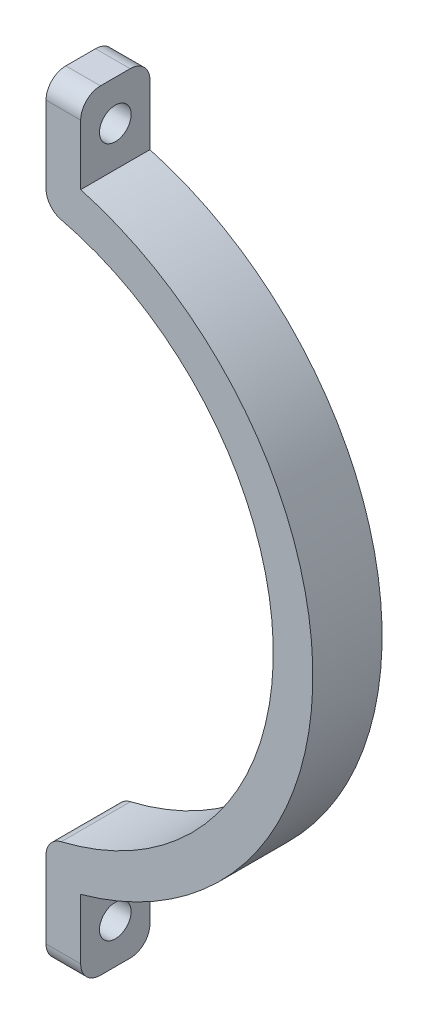
SolidWorks part; units mm, degrees
ref_plane "前视基准面" through (0, 0, 0) normal (0, 0, 1) x (1, 0, 0)
ref_plane "上视基准面" through (0, 0, 0) normal (0, 1, 0) x (1, 0, 0)
ref_plane "右视基准面" through (0, 0, 0) normal (1, 0, 0) x (0, 0, -1)
sketch "草图1" plane through (0, 0, 0) normal (0, 0, 1) x (1, 0, 0)
  line L0 (0, 148.5) -> (0, -94.9538) construction
  line L1 (105, -148.5) -> (-105, -148.5) construction
  line L2 (105, -148.5) -> (105, 148.5) construction
  line L3 (105, 148.5) -> (-105, 148.5) construction
  line L4 (-105, -148.5) -> (-105, 148.5) construction
  line L5 (105, -148.5) -> (-105, 148.5) construction
  line L6 (105, 148.5) -> (-105, -148.5) construction
  line L7 (35.8892, 121.6645) -> (-35.8892, 121.6645)
  line L8 (-35.8892, 121.6645) -> (-66.9017, 102.292)
  line L9 (-75, 40.9339) -> (-75, 31.2613)
  line L10 (-66.9017, 102.292) -> (-66.9017, 52.8701)
  line L11 (75, 40.9339) -> (75, 31.2613)
  line L12 (66.9017, 102.292) -> (66.9017, 52.8701)
  line L13 (35.8892, 121.6645) -> (66.9017, 102.292)
  line L14 (-75, 31.2613) -> (75, 31.2613)
  line L15 (-60, -148.5) -> (-60, -91.8129)
  line L16 (-75, 23.94) -> (75, 23.94)
  line L17 (-75, 23.94) -> (-75, 10.5626)
  line L18 (-38.8455, -105.5906) -> (-66.4608, -113.7617)
  line L19 (-66.4608, -113.7617) -> (-70.1743, -102.7328)
  line L20 (75, 23.94) -> (75, 10.5626)
  line L21 (66.4608, -113.7617) -> (70.1743, -102.7328)
  line L22 (38.8455, -105.5906) -> (66.4608, -113.7617)
  line L23 (-105, 93.0519) -> (105, 93.0519)
  line L24 (-105, 63.0519) -> (105, 63.0519)
  line L25 (-105, -90.0629) -> (-70.5337, -90.0629)
  line L26 (-105, -60.0629) -> (-67.4027, -60.0629)
  line L27 (60, -148.5) -> (60, 148.5)
  line L28 (-60, -58.3129) -> (-45, -58.3129)
  line L29 (-60, -61.8129) -> (-45, -61.8129)
  line L30 (-36, -58.3129) -> (-21, -58.3129)
  line L31 (-36, -61.8129) -> (-21, -61.8129)
  line L32 (-60, -88.3129) -> (-45, -88.3129)
  line L33 (-60, -91.8129) -> (-45, -91.8129)
  line L34 (-36, -88.3129) -> (-21, -88.3129)
  line L35 (-36, -91.8129) -> (-21, -91.8129)
  line L36 (-60, -58.3129) -> (-60, 148.5)
  line L37 (-19.25, -90.0629) -> (105, -90.0629)
  line L38 (-19.25, -60.0629) -> (19.25, -60.0629)
  line L39 (-60, -88.3129) -> (-60, -61.8129)
  line L40 (21, -58.3129) -> (36, -58.3129)
  line L41 (45, -58.3129) -> (60, -58.3129)
  line L42 (60, -61.8129) -> (45, -61.8129)
  line L43 (36, -61.8129) -> (21, -61.8129)
  line L44 (21, -88.3129) -> (36, -88.3129)
  line L45 (21, -91.8129) -> (36, -91.8129)
  line L46 (45, -88.3129) -> (60, -88.3129)
  line L47 (45, -91.8129) -> (60, -91.8129)
  line L48 (37.75, -60.0629) -> (43.25, -60.0629)
  line L49 (58.25, -60.0629) -> (105, -60.0629)
  line L50 (-60, 94.8019) -> (-45, 94.8019)
  line L51 (-36, 94.8019) -> (-21, 94.8019)
  line L52 (-60, 91.3019) -> (-45, 91.3019)
  line L53 (-36, 91.3019) -> (-21, 91.3019)
  line L54 (-60, 64.8019) -> (-45, 64.8019)
  line L55 (-60, 61.3019) -> (-45, 61.3019)
  line L56 (-36, 64.8019) -> (-21, 64.8019)
  line L57 (-36, 61.3019) -> (-21, 61.3019)
  line L58 (21, 94.8019) -> (36, 94.8019)
  line L59 (21, 91.3019) -> (36, 91.3019)
  line L60 (45, 94.8019) -> (60, 94.8019)
  line L61 (45, 91.3019) -> (60, 91.3019)
  line L62 (21, 61.3019) -> (36, 61.3019)
  line L63 (21, 64.8019) -> (36, 64.8019)
  line L64 (45, 61.3019) -> (60, 61.3019)
  line L65 (45, 64.8019) -> (60, 64.8019)
  line L66 (-33.1709, -104.7687) -> (33.1709, -104.7687)
  line L67 (0, -104.7687) -> (0, -148.5) construction
  arc A0 (-75, 40.9339) -> (-66.9017, 52.8701) centre (-79.7474, 52.8701) ccw
  arc A1 (75, 40.9339) -> (66.9017, 52.8701) centre (79.7474, 52.8701) cw
  arc A3 (-60, -88.3129) -> (-60, -91.8129) centre (-60, -90.0629) ccw
  arc A4 (-60, -58.3129) -> (-60, -61.8129) centre (-60, -60.0629) ccw
  circle A5 centre (-60, 63.0519) radius 1.75
  circle A6 centre (-60, 93.0519) radius 1.75
  circle A7 centre (60, 93.0519) radius 1.75
  circle A8 centre (60, 63.0519) radius 1.75
  arc A9 (60, -91.8129) -> (60, -88.3129) centre (60, -90.0629) ccw
  arc A10 (60, -61.8129) -> (60, -58.3129) centre (60, -60.0629) ccw
  arc A11 (-36, -58.3129) -> (-36, -61.8129) centre (-36, -60.0629) ccw
  arc A12 (-36, -88.3129) -> (-36, -91.8129) centre (-36, -90.0629) ccw
  arc A13 (36, -61.8129) -> (36, -58.3129) centre (36, -60.0629) ccw
  arc A14 (36, -91.8129) -> (36, -88.3129) centre (36, -90.0629) ccw
  arc A15 (-45, -61.8129) -> (-45, -58.3129) centre (-45, -60.0629) ccw
  arc A16 (-21, -61.8129) -> (-21, -58.3129) centre (-21, -60.0629) ccw
  arc A17 (-45, -91.8129) -> (-45, -88.3129) centre (-45, -90.0629) ccw
  arc A18 (-21, -91.8129) -> (-21, -88.3129) centre (-21, -90.0629) ccw
  arc A19 (45, -58.3129) -> (45, -61.8129) centre (45, -60.0629) ccw
  arc A20 (21, -58.3129) -> (21, -61.8129) centre (21, -60.0629) ccw
  arc A21 (21, -88.3129) -> (21, -91.8129) centre (21, -90.0629) ccw
  arc A22 (45, -88.3129) -> (45, -91.8129) centre (45, -90.0629) ccw
  circle A23 centre (-36, 93.0519) radius 1.75
  circle A24 centre (-36, 63.0519) radius 1.75
  circle A25 centre (36, 93.0519) radius 1.75
  circle A26 centre (36, 63.0519) radius 1.75
  circle A27 centre (-45, 93.0519) radius 1.75
  circle A28 centre (-21, 93.0519) radius 1.75
  circle A29 centre (-45, 63.0519) radius 1.75
  circle A30 centre (-21, 63.0519) radius 1.75
  circle A31 centre (21, 93.0519) radius 1.75
  circle A32 centre (21, 63.0519) radius 1.75
  circle A33 centre (45, 93.0519) radius 1.75
  circle A34 centre (45, 63.0519) radius 1.75
  arc A35 (33.1709, -104.7687) -> (38.8455, -105.5906) centre (33.1709, -124.7687) cw
  arc A36 (-33.1709, -104.7687) -> (-38.8455, -105.5906) centre (-33.1709, -124.7687) ccw
  spline S0 degree 3 poles (-75, 10.5626) (-72.6959, 1.9073) (-70.3396, -13.3728) (-67.1028, -43.6255) (-66.7657, -72.9327) (-71.8903, -95.1489) (-70.1743, -102.7328) knots 0 0 0 0 0.235247 0.406294 0.801186 1 1 1 1
  spline S1 degree 3 poles (75, 10.5626) (72.6959, 1.9073) (70.3396, -13.3728) (67.1028, -43.6255) (66.7657, -72.9327) (71.8903, -95.1489) (70.1743, -102.7328) knots 0 0 0 0 0.235247 0.406294 0.801186 1 1 1 1
  point P0 (0, 0)
  point P27 (0, 121.6645)
  point P42 (0, -94.0966)
  dimension "D1" = 60
  dimension "D4" = 20
  dimension "D5" = 24
  dimension "D7" = 24
  dimension "D9" = 15
  dimension "D10" = 15
  dimension "D13" = 24
  dimension "D17" = 15
  dimension "D2" = 30
  dimension "D3" = 30
  dimension "D6" = 24
  dimension "D8" = 24
  dimension "D11" = 15
  dimension "D12" = 15
  dimension "D14" = 24
  dimension "D15" = 24
  dimension "D16" = 24
  dimension "D18" = 15
  dimension "D19" = 15
  dimension "D20" = 15
  dimension "D21" = 15
  dimension "D22" = 15
  dimension "D23" = 15
  dimension "D24" = 15
  dimension "D25" = 15
  dimension "D26" = 15
  dimension "D27" = 15
  dimension "D28" = 15
  dimension "D29" = 3.5
  dimension "D30" = 3.5
  dimension "D31" = 3.5
extrude "凸台-拉伸1" add sketch "草图1" along normal blind 3 contours A34 L24 A26 L62 A32 A30 L57 A24 A29 L55 L36 L14 L27 L64 | A5 L24 L10 A0 L9 L14 L36 | A6 L23 L10 L24 A5 L36 | A6 L36 L8 L10 L23 | A33 L60 L27 L13 L7 L8 L36 L50 A27 L23 A23 L51 A28 A31 L58 A25 | A34 L65 L27 L61 A33 L23 A25 L59 A31 A28 L53 A23 A27 L52 L36 L54 A29 L24 A24 L56 A30 A32 L63 A26 | A7 L23 L12 L13 L27 | A8 L24 L12 L23 A7 L27 | A8 L27 L14 L11 A1 L12 L24 | A22 L46 L27 L42 A19 A13 L43 A20 A16 L31 A11 L30 L40 L41 L16 L36 L28 A15 L29 L39 L32 A17 L33 L15 L18 L22 L47 A14 L45 A21 A18 L35 A12 L34 | L17 S0 L19 L18 L15 A3 L39 A4 L36 L16 | S1 L20 L16 L27 A10 L49 | S1 L49 A10 L27 A9 L37 | S1 L37 A9 L27 L22 L21 region at (0, 106.7597, 0) region at (63.3118, 98.9762, 0) region at (-63.3118, 98.9762, 0) region at (63.5153, 78.0519, 0) region at (-63.5153, 78.0519, 0) region at (65.7633, 44.067, 0) region at (0, 78.0519, 0) region at (-65.7633, 44.067, 0) region at (0, 46.6707, 0) region at (0, -40.0712, 0) region at (65.6849, -11.6712, 0) region at (-65.3451, -38.0027, 0) region at (64.4303, -76.0355, 0) region at (65.0264, -100.7629, 0)
sketch "草图7" plane through (0, 0, 0) normal (0, 0, -1) x (-1, 0, 0)
  line L0 (0, 121.6645) -> (0, -104.7687) construction
  line L1 (-35.8892, 121.6645) -> (35.8892, 121.6645) construction
  line L2 (33.1709, -104.7687) -> (-33.1709, -104.7687) construction
  line L3 (0, 41.2613) -> (-21, 41.2613) construction
  line L4 (0, 41.2613) -> (21, 41.2613) construction
  line L5 (0, 13.94) -> (-21, 13.94) construction
  line L6 (0, 13.94) -> (21, 13.94) construction
  line L7 (75, 23.94) -> (-75, 23.94) construction
  line L8 (75, 31.2613) -> (-75, 31.2613) construction
  circle A0 centre (-21, 41.2613) radius 2.25
  circle A1 centre (21, 41.2613) radius 2.25
  circle A2 centre (-21, 13.94) radius 2.25
  circle A3 centre (21, 13.94) radius 2.25
  dimension "D1" = 10
  dimension "D2" = 10
extrude "切除-拉伸2" cut sketch "草图7" against normal through all
sketch "草图8" plane through (0, 0, 3) normal (0, 0, 1) x (1, 0, 0)
  line L0 (0, 121.6645) -> (0, -1.9696) construction
  line L1 (35.8892, 121.6645) -> (-35.8892, 121.6645) construction
  line L2 (-33.1709, -104.7687) -> (33.1709, -104.7687) construction
  line L3 (-33.409, 20.409) -> (-12.6214, -0.3786)
  line L4 (31.818, -51.182) -> (-31.818, -51.182)
  line L5 (35, -48) -> (35, 15.6418)
  line L8 (-35, 18.818) -> (-12.6214, -3.5605) construction
  line L9 (-33.409, -52.773) -> (-12.5737, -31.9377)
  line L10 (-36.591, 17.227) -> (-15.8034, -3.5605)
  line L11 (33.4105, 20.4105) -> (12.573, -0.427)
  line L12 (15.803, -3.5609) -> (36.5881, 17.2241)
  line L13 (31.8195, 18.8195) -> (-31.818, 18.818)
  line L14 (-15.8038, -28.8038) -> (-36.591, -49.591)
  line L15 (12.5534, -31.9174) -> (33.409, -52.773)
  line L16 (34.9993, 18.8173) -> (12.6207, -3.5613) construction
  line L17 (0, -30.3951) -> (0, -104.7687) construction
  line L18 (-35, -48) -> (-35, 15.636)
  line L19 (-11.9624, -1.9696) -> (-14.2124, -1.9696) construction
  line L20 (15.8034, -28.8034) -> (36.591, -49.591)
  line L21 (14.2117, -30.3951) -> (11.9607, -30.3951) construction
  line L22 (14.2117, -30.3951) -> (14.2117, -28.1441) construction
  line L23 (14.2117, -1.9696) -> (11.9612, -1.9696) construction
  line L24 (-14.2124, -30.3951) -> (-14.2124, -28.1446) construction
  line L25 (14.2117, -30.3951) -> (12.62, -28.8034) construction
  line L26 (14.2117, -1.9696) -> (12.6204, -3.5609) construction
  line L27 (12.6207, -28.8027) -> (35, -51.182) construction
  line L28 (-12.6215, -3.5606) -> (-14.2124, -1.9696) construction
  line L29 (-14.2124, -4.2196) -> (-14.2124, -1.9696) construction
  line L30 (-12.6214, -28.8034) -> (-35, -51.182) construction
  line L31 (-12.6211, -28.8037) -> (-14.2124, -30.3951) construction
  line L32 (-11.9619, -30.3951) -> (-14.2124, -30.3951) construction
  line L33 (14.2117, -4.2201) -> (14.2117, -1.9696) construction
  line L34 (11.0312, -30.3951) -> (0, -30.3951) construction
  arc A0 (-33.409, 20.409) -> (-36.591, 17.227) centre (-35, 18.818) ccw
  arc A1 (36.5881, 17.2241) -> (33.4105, 20.4105) centre (34.9993, 18.8173) ccw
  arc A2 (-36.591, -49.591) -> (-33.409, -52.773) centre (-35, -51.182) ccw
  arc A3 (33.409, -52.773) -> (36.591, -49.591) centre (35, -51.182) ccw
  arc A4 (-15.8034, -3.5605) -> (-12.6214, -0.3786) centre (-14.2124, -1.9696) ccw
  arc A5 (12.6692, -0.3308) -> (15.803, -3.5609) centre (14.2117, -1.9696) ccw
  arc A6 (-12.6699, -32.0338) -> (-15.8038, -28.8038) centre (-14.2124, -30.3951) ccw
  arc A7 (15.8034, -28.8034) -> (12.6894, -32.0534) centre (14.2117, -30.3951) ccw
  circle A8 centre (-0.0004, -16.1823) radius 8
  point P6 (0, -16.182)
  point P13 (-0.0004, -16.1823)
extrude "切除-拉伸3" cut sketch "草图8" against normal through all contours L10 A4 L3 A0 | L11 A5 L12 A1 | L20 A7 L15 A3 | L9 A6 L14 A2 | A8 region at (-24.6062, 8.4242, 3) region at (24.6054, 8.4234, 3) region at (-24.6061, -40.7881, 3) region at (24.6056, -40.7877, 3) region at (-0.0004, -16.1823, 3)
sketch "草图9" plane through (0, 0, 3) normal (0, 0, 1) x (1, 0, 0)
  line L0 (-70.7828, -98.747) -> (70.7828, -98.747) construction
  line L1 (0, -98.747) -> (0, -104.7687) construction
  line L2 (55, -100.497) -> (20, -100.497)
  line L3 (-55, -96.997) -> (-20, -96.997)
  line L4 (-55, -100.497) -> (-20, -100.497)
  line L5 (-33.1709, -104.7687) -> (33.1709, -104.7687) construction
  line L6 (55, -96.997) -> (20, -96.997)
  arc A0 (-55, -96.997) -> (-55, -100.497) centre (-55, -98.747) ccw
  arc A1 (-20, -100.497) -> (-20, -96.997) centre (-20, -98.747) ccw
  arc A2 (20, -100.497) -> (20, -96.997) centre (20, -98.747) cw
  arc A3 (55, -96.997) -> (55, -100.497) centre (55, -98.747) cw
  spline S0 degree 3 poles (-75, 10.5626) (-72.6959, 1.9073) (-70.3396, -13.3728) (-67.1028, -43.6255) (-66.7657, -72.9327) (-71.8903, -95.1489) (-70.1743, -102.7328) knots 0 0 0 0 0.235247 0.406294 0.801186 1 1 1 1 construction
  spline S1 degree 3 poles (75, 10.5626) (72.6959, 1.9073) (70.3396, -13.3728) (67.1028, -43.6255) (66.7657, -72.9327) (71.8903, -95.1489) (70.1743, -102.7328) knots 0 0 0 0 0.235247 0.406294 0.801186 1 1 1 1 construction
  dimension "D1" = 35
  dimension "D2" = 20
extrude "切除-拉伸4" cut sketch "草图9" against normal blind 3
sketch "草图10" plane through (0, 0, 3) normal (0, 0, 1) x (1, 0, 0)
  line L0 (-21, -60.0629) -> (-21, -90.0629) construction
  line L1 (21, -60.0629) -> (21, -90.0629) construction
  line L2 (-21, -75.0629) -> (-17.5, -75.0629) construction
  line L4 (12.5, -80.0629) -> (-12.5, -80.0629)
  line L6 (12.5, -70.0629) -> (-12.5, -70.0629)
  line L11 (17.5, -75.0629) -> (21, -75.0629) construction
  arc A0 (-12.5, -70.0629) -> (-12.5, -80.0629) centre (-12.5, -75.0629) ccw
  arc A1 (12.5, -80.0629) -> (12.5, -70.0629) centre (12.5, -75.0629) ccw
  point P11 (0, -75.0629)
extrude "切除-拉伸5" cut sketch "草图10" against normal blind 3
sketch "草图11" plane through (0, 0, 3) normal (0, 0, 1) x (1, 0, 0)
  line L0 (-21, 93.0519) -> (-21, 63.0519) construction
  line L1 (21, 93.0519) -> (21, 63.0519) construction
  line L2 (-21, 78.0519) -> (-20, 78.0519) construction
  line L4 (15, 73.0519) -> (-15, 73.0519)
  line L6 (15, 83.0519) -> (-15, 83.0519)
  line L10 (20, 78.0519) -> (21, 78.0519) construction
  arc A0 (-15, 83.0519) -> (-15, 73.0519) centre (-15, 78.0519) ccw
  arc A1 (15, 73.0519) -> (15, 83.0519) centre (15, 78.0519) ccw
  point P10 (0, 78.0519)
  dimension "D1" = 30
extrude "切除-拉伸8" cut sketch "草图11" against normal blind 3
sketch "草图12" plane through (0, 0, 3) normal (0, 0, 1) x (1, 0, 0)
  line L0 (0, 121.6645) -> (0, 83.0519) construction
  line L1 (35.8892, 121.6645) -> (-35.8892, 121.6645) construction
  line L2 (15, 83.0519) -> (-15, 83.0519) construction
  circle A0 centre (0, 106.3718) radius 11 construction
  circle A1 centre (0, 106.3718) radius 8 construction
  circle A2 centre (0, 114.3718) radius 1.7
  circle A3 centre (0, 98.3718) radius 1.7
  circle A4 centre (8, 106.3718) radius 1.7
  circle A5 centre (-8, 106.3718) radius 1.7
extrude "切除-拉伸9" cut sketch "草图12" against normal blind 3
sketch "草图13" plane through (0, 0, 3) normal (0, 0, 1) x (1, 0, 0)
  line L0 (0, -104.7687) -> (0, -80.0629) construction
  line L1 (-33.1709, -104.7687) -> (33.1709, -104.7687) construction
  line L2 (-12.5, -80.0629) -> (12.5, -80.0629) construction
  circle A0 centre (0, -92.4158) radius 8 construction
  circle A1 centre (0, -84.4158) radius 1.7
  circle A2 centre (8, -92.4158) radius 1.7
  circle A3 centre (0, -100.4158) radius 1.7
  circle A4 centre (-8, -92.4158) radius 1.7
extrude "切除-拉伸11" cut sketch "草图13" against normal blind 3
sketch "草图14" plane through (0, 0, 3) normal (0, 0, 1) x (1, 0, 0)
  line L0 (0, 23.94) -> (0, -104.7687) construction
  line L1 (-55.4755, 8.9197) -> (-55.4755, -46.0803)
  line L2 (-58.9755, 8.9197) -> (-58.9755, -46.0803)
  line L3 (-75, 23.94) -> (75, 23.94) construction
  line L4 (-33.1709, -104.7687) -> (33.1709, -104.7687) construction
  line L5 (58.9755, 8.9197) -> (58.9755, -46.0803)
  line L6 (55.4755, 8.9197) -> (55.4755, -46.0803)
  arc A0 (-55.4755, 8.9197) -> (-58.9755, 8.9197) centre (-57.2255, 8.9197) ccw
  arc A1 (-58.9755, -46.0803) -> (-55.4755, -46.0803) centre (-57.2255, -46.0803) ccw
  arc A2 (58.9755, -46.0803) -> (55.4755, -46.0803) centre (57.2255, -46.0803) cw
  arc A3 (55.4755, 8.9197) -> (58.9755, 8.9197) centre (57.2255, 8.9197) cw
extrude "切除-拉伸12" cut sketch "草图14" against normal through all
fillet "圆角1" radius 2 2 edges at (75, 31.2613, 1.5) (-75, 31.2613, 1.5)
fillet "圆角2" radius 2 2 edges at (-75, 23.94, 1.5) (75, 23.94, 1.5)
sketch "草图15" plane through (0, 0, 0) normal (0, 0, -1) x (-1, 0, 0)
  line L0 (0, 121.6645) -> (0, 31.2613) construction
  line L1 (-35.8892, 121.6645) -> (35.8892, 121.6645) construction
  line L2 (73, 31.2613) -> (-73, 31.2613) construction
  line L3 (-27.5188, 121.6645) -> (-63.6963, 99.0657) construction
  line L4 (-35.8892, 121.6645) -> (-66.9017, 102.292) construction
  line L5 (-61.1842, 102.4035) -> (-34.7748, 118.9006)
  line L6 (-59.5948, 99.8591) -> (-33.1854, 116.3562)
  line L7 (27.5188, 121.6645) -> (63.6963, 99.0657) construction
  line L8 (59.5948, 99.8591) -> (33.1854, 116.3562)
  line L9 (61.1842, 102.4035) -> (34.7748, 118.9006)
  arc A0 (-61.1842, 102.4035) -> (-59.5948, 99.8591) centre (-60.3895, 101.1313) ccw
  arc A1 (-33.1854, 116.3562) -> (-34.7748, 118.9006) centre (-33.9801, 117.6284) ccw
  arc A2 (33.1854, 116.3562) -> (34.7748, 118.9006) centre (33.9801, 117.6284) cw
  arc A3 (61.1842, 102.4035) -> (59.5948, 99.8591) centre (60.3895, 101.1313) cw
extrude "切除-拉伸13" cut sketch "草图15" against normal through all
sketch "草图16" plane through (0, 0, 0) normal (0, 0, -1) x (-1, 0, 0)
  line L0 (0, 121.6645) -> (0, 31.2613) construction
  line L1 (-35.8892, 121.6645) -> (35.8892, 121.6645) construction
  line L2 (73, 31.2613) -> (-73, 31.2613) construction
  line L3 (-21, 41.2613) -> (-66.71, 41.2613) construction
  line L4 (-61.517, 42.7613) -> (-32.0563, 42.7613)
  line L5 (-61.517, 39.7613) -> (-32.0563, 39.7613)
  line L6 (21, 41.2613) -> (66.71, 41.2613) construction
  line L7 (61.517, 39.7613) -> (32.0563, 39.7613)
  line L8 (61.517, 42.7613) -> (32.0563, 42.7613)
  arc A0 (-61.517, 42.7613) -> (-61.517, 39.7613) centre (-61.517, 41.2613) ccw
  arc A1 (-32.0563, 39.7613) -> (-32.0563, 42.7613) centre (-32.0563, 41.2613) ccw
  arc A2 (32.0563, 39.7613) -> (32.0563, 42.7613) centre (32.0563, 41.2613) cw
  arc A3 (61.517, 42.7613) -> (61.517, 39.7613) centre (61.517, 41.2613) cw
extrude "切除-拉伸14" cut sketch "草图16" against normal through all
sketch "草图17" plane through (0, 0, 0) normal (0, 0, -1) x (-1, 0, 0)
  text T0 "Y" font "黑体" height in points 72
extrude "切除-拉伸15" cut sketch "草图17" against normal through all
sketch "草图18" plane through (0, 0, 0) normal (0, 0, -1) x (-1, 0, 0)
  text T0 "H" font "黑体" height in points 72
extrude "切除-拉伸16" cut sketch "草图18" against normal through all
ref_plane "基准面1" through (0, 0, -10) normal (0, 0, -1) x (-1, 0, 0)
sketch "草图19" plane through (0, 0, -10) normal (0, 0, -1) x (-1, 0, 0)
  line L0 (-58.9755, -46.0803) -> (-58.9755, 8.9197) construction
  line L1 (-55.4755, 8.9197) -> (-55.4755, -46.0803) construction
  line L2 (-58.9755, -30.086) -> (-58.9755, -15.086)
  line L3 (-55.4755, -15.086) -> (-55.4755, -30.086)
  line L4 (-57.2255, -15.086) -> (-57.2255, -30.086) construction
  line L5 (-55.4755, -15.086) -> (-55.4755, -30.086)
  line L6 (-58.9755, -15.086) -> (-58.9755, -30.086)
  line L7 (-61.7255, -34.086) -> (-89.4178, -34.086) construction
  line L8 (-61.7255, -34.086) -> (-52.7255, -34.086)
  line L10 (-61.7255, -11.086) -> (-52.7255, -11.086)
  line L11 (-52.7255, -34.086) -> (-52.7255, -11.086)
  line L12 (-61.7255, -34.086) -> (-52.7255, -11.086) construction
  line L13 (-58.9755, -18.1137) -> (-52.7255, -34.086) construction
  line L14 (-75, 21.94) -> (-75, 10.5626) construction
  line L15 (-61.7255, -11.086) -> (-75, -11.086)
  line L17 (-61.7255, -34.086) -> (-75, -34.086)
  line L18 (-75, -11.086) -> (-75, -34.086)
  arc A0 (-58.9755, -46.0803) -> (-55.4755, -46.0803) centre (-57.2255, -46.0803) ccw construction
  arc A1 (-55.4755, 8.9197) -> (-58.9755, 8.9197) centre (-57.2255, 8.9197) ccw construction
  arc A2 (-58.9755, -46.0803) -> (-55.4755, -46.0803) centre (-57.2255, -46.0803) ccw
  arc A3 (-55.4755, 8.9197) -> (-58.9755, 8.9197) centre (-57.2255, 8.9197) ccw
  arc A4 (-55.4755, -15.086) -> (-58.9755, -15.086) centre (-57.2255, -15.086) ccw
  arc A5 (-58.9755, -30.086) -> (-55.4755, -30.086) centre (-57.2255, -30.086) ccw
  point P7 (-57.2255, -22.586)
  dimension "D1" = 15
  dimension "D2" = 0
extrude "凸台-拉伸2" add sketch "草图19" along normal blind 4 separate body contours L15 L18 L17 L8 L11 L10 A5 L2 A4 L3 region at (64.7786, -22.586, -10)
sketch "草图20" plane through (0, 0, -14) normal (0, 0, -1) x (-1, 0, 0)
  line L0 (-52.7255, -34.086) -> (-75, -34.086) construction
  line L1 (-75, -11.086) -> (-71, -11.086)
  line L2 (-75, -11.086) -> (-75, -34.086)
  line L3 (-75, -34.086) -> (-71, -34.086)
  line L4 (-71, -11.086) -> (-71, -34.086)
extrude "凸台-拉伸3" add sketch "草图20" along normal blind 5
sketch "草图21" plane through (0, 0, -19) normal (0, 0, -1) x (-1, 0, 0)
  line L0 (-71, -22.586) -> (-170.2086, -22.586) construction
  line L1 (-71, -34.086) -> (-71, -11.086) construction
  line L2 (-75, -11.086) -> (-75, -34.086) construction
  line L3 (-102.0333, -61.5135) -> (-98.5333, -61.5135)
  line L4 (-108.0333, 16.3416) -> (-108.0333, 4.9579)
  line L5 (-102.0333, 16.3416) -> (-102.0333, 5.3974)
  line L6 (-111.5333, 16.3416) -> (-111.5333, 8.2553)
  line L7 (-98.5333, 16.3416) -> (-98.5333, 9.1008)
  line L8 (-111.5333, 16.3416) -> (-108.0333, 16.3416)
  line L9 (-102.0333, 16.3416) -> (-98.5333, 16.3416)
  line L11 (-111.5333, -61.5135) -> (-108.0333, -61.5135)
  line L12 (-111.5333, -53.4272) -> (-111.5333, -61.5135)
  line L13 (-108.0333, -50.1298) -> (-108.0333, -61.5135)
  line L14 (-102.0333, -50.5693) -> (-102.0333, -61.5135)
  line L15 (-98.5333, -54.2727) -> (-98.5333, -61.5135)
  arc A0 (-108.0333, 4.9579) -> (-108.0333, -50.1298) centre (-103, -22.586) ccw
  arc A1 (-111.5333, 8.2553) -> (-111.5333, -53.4272) centre (-103, -22.586) ccw
  arc A2 (-102.0333, -50.5693) -> (-102.0333, 5.3974) centre (-103, -22.586) ccw
  arc A3 (-98.5333, -54.2727) -> (-98.5333, 9.1008) centre (-103, -22.586) ccw
  dimension "D1" = 3.5
  dimension "D2" = 3.5
  dimension "D3" = 6
extrude "凸台-拉伸4" add sketch "草图21" along normal blind 7
sketch "草图22" plane through (0, 0, -19) normal (0, 0, 1) x (1, 0, 0)
  line L0 (75, -22.586) -> (75, -34.086) construction
  line L1 (75, -34.086) -> (73.1378, -34.086) construction
  line L2 (98.5333, -54.2727) -> (98.5333, -61.5135) construction
  line L3 (98.5333, -61.5135) -> (102.0333, -61.5135) construction
  line L4 (102.0333, -61.5135) -> (102.0333, -50.5693) construction
  line L5 (73.1378, -11.086) -> (75, -11.086) construction
  line L6 (75, -11.086) -> (75, -22.586) construction
  line L7 (102.0333, 5.3974) -> (102.0333, 16.3416) construction
  line L8 (102.0333, 16.3416) -> (98.5333, 16.3416) construction
  line L9 (98.5333, 16.3416) -> (98.5333, 9.1008) construction
  line L10 (75, -22.586) -> (75, -34.086)
  line L11 (75, -34.086) -> (73.1378, -34.086)
  line L12 (98.5333, -54.2727) -> (98.5333, -61.5135)
  line L13 (98.5333, -61.5135) -> (102.0333, -61.5135)
  line L14 (102.0333, -61.5135) -> (102.0333, -50.5693)
  line L15 (73.1378, -11.086) -> (75, -11.086)
  line L16 (75, -11.086) -> (75, -22.586)
  line L17 (102.0333, 5.3974) -> (102.0333, 16.3416)
  line L18 (102.0333, 16.3416) -> (98.5333, 16.3416)
  line L19 (98.5333, 16.3416) -> (98.5333, 9.1008)
  line L20 (75, -11.086) -> (77.4706, -11.086)
  line L21 (75, -34.086) -> (77.4706, -34.086)
  arc A1 (75, -22.586) -> (102.0333, -50.5693) centre (103, -22.586) ccw construction
  arc A2 (102.0333, 5.3974) -> (75, -22.586) centre (103, -22.586) ccw construction
  arc A5 (75, -22.586) -> (77.4706, -34.086) centre (103, -22.586) ccw
  arc A6 (77.4706, -11.086) -> (75, -22.586) centre (103, -22.586) ccw
  line M9 (75, -11.086) -> (75, -22.586)
  arc M10 (75, -22.586) -> (102.0333, 5.3974) centre (103, -22.586) cw
extrude "凸台-拉伸5" add sketch "草图22" along normal up to surface (9 mm away) contours L20 M9 M10 | A5 L10 L21 region at (75.7352, -31.2369, -19) region at (75.7352, -13.935, -19) up to face at (57.2255, -22.586, -10)
sketch "草图23" plane through (0, 0, -19) normal (0, 0, -1) x (-1, 0, 0)
  line L0 (-71, -22.586) -> (-71, -11.086) construction
  line L1 (-71, -11.086) -> (-73.1378, -11.086) construction
  line L2 (-73.1378, -34.086) -> (-71, -34.086) construction
  line L3 (-71, -34.086) -> (-71, -22.586) construction
  line L4 (-71, -22.586) -> (-71, -11.086)
  line L5 (-71, -11.086) -> (-73.1378, -11.086)
  line L6 (-73.1378, -34.086) -> (-71, -34.086)
  line L7 (-71, -34.086) -> (-71, -22.586)
  arc A0 (-71, -22.586) -> (-73.1378, -11.086) centre (-103, -22.586) ccw construction
  arc A1 (-73.1378, -34.086) -> (-71, -22.586) centre (-103, -22.586) ccw construction
  arc A2 (-71, -22.586) -> (-73.1378, -11.086) centre (-103, -22.586) ccw
  arc A3 (-73.1378, -34.086) -> (-71, -22.586) centre (-103, -22.586) ccw
  arc M1 (-71, -22.586) -> (-73.1378, -34.086) centre (-103, -22.586) cw
  line M2 (-73.1378, -34.086) -> (-71, -34.086)
  line M3 (-71, -34.086) -> (-71, -22.586)
extrude "切除-拉伸17" cut sketch "草图23" against normal up to surface (5 mm away) contours A2 L4 L5 | M3 M1 M2 region at (71.6375, -13.9414, -19) region at (71.6375, -31.2305, -19) up to face at (61.8628, -22.586, -14)
sketch "草图24" plane through (0, 0, -26) normal (0, 0, -1) x (-1, 0, 0)
  line L0 (-73.1378, -11.086) -> (-77.4706, -11.086)
  line L1 (-73.1378, -34.086) -> (-77.4706, -34.086)
  line L6 (-102.0333, -50.5693) -> (-102.0333, -61.5135)
  line L7 (-102.0333, -61.5135) -> (-98.5333, -61.5135)
  line L8 (-98.5333, -61.5135) -> (-98.5333, -54.2727)
  line L9 (-98.5333, 9.1008) -> (-98.5333, 16.3416)
  line L10 (-98.5333, 16.3416) -> (-102.0333, 16.3416)
  line L11 (-102.0333, 16.3416) -> (-102.0333, 5.3974)
  line L12 (-102.0333, -50.5693) -> (-102.0333, -61.5135)
  line L13 (-102.0333, -61.5135) -> (-98.5333, -61.5135)
  line L14 (-98.5333, -61.5135) -> (-98.5333, -54.2727)
  line L15 (-98.5333, 9.1008) -> (-98.5333, 16.3416)
  line L16 (-98.5333, 16.3416) -> (-102.0333, 16.3416)
  line L17 (-102.0333, 16.3416) -> (-102.0333, 5.3974)
  arc A2 (-102.0333, -50.5693) -> (-102.0333, 5.3974) centre (-103, -22.586) ccw
  arc A3 (-98.5333, -54.2727) -> (-98.5333, 9.1008) centre (-103, -22.586) ccw
  arc A4 (-77.4706, -34.086) -> (-77.4706, -11.086) centre (-103, -22.586) ccw
  arc A5 (-73.1378, -34.086) -> (-73.1378, -11.086) centre (-103, -22.586) ccw
  arc M9 (-102.0333, 5.3974) -> (-102.0333, -50.5693) centre (-103, -22.586) cw
  arc M13 (-98.5333, -54.2727) -> (-98.5333, 9.1008) centre (-103, -22.586) ccw
  dimension "D1" = 0
extrude "凸台-拉伸6" add sketch "草图24" along normal blind 5 contours L1 L0 M13 M9 region at (73.7718, -22.586, -26)
sketch "草图25" plane through (0, 0, -31) normal (0, 0, -1) x (-1, 0, 0)
  line L0 (-111.5333, -53.4272) -> (-111.5333, -61.5135) construction
  line L1 (-111.5333, -61.5135) -> (-108.0333, -61.5135) construction
  line L2 (-108.0333, -61.5135) -> (-108.0333, -50.1298) construction
  line L3 (-108.0333, 4.9579) -> (-108.0333, 16.3416) construction
  line L4 (-108.0333, 16.3416) -> (-111.5333, 16.3416) construction
  line L5 (-111.5333, 16.3416) -> (-111.5333, 8.2553) construction
  line L6 (-73.1378, -34.086) -> (-77.4706, -34.086) construction
  line L7 (-102.0333, -50.5693) -> (-102.0333, -61.5135) construction
  line L8 (-102.0333, -61.5135) -> (-98.5333, -61.5135) construction
  line L9 (-98.5333, -61.5135) -> (-98.5333, -54.2727) construction
  line L10 (-77.4706, -34.086) -> (-73.1378, -34.086) construction
  line L11 (-73.1378, -11.086) -> (-77.4706, -11.086) construction
  line L12 (-77.4706, -11.086) -> (-73.1378, -11.086) construction
  line L13 (-98.5333, 9.1008) -> (-98.5333, 16.3416) construction
  line L14 (-98.5333, 16.3416) -> (-102.0333, 16.3416) construction
  line L15 (-102.0333, 16.3416) -> (-102.0333, 5.3974) construction
  line L16 (-111.5333, -53.4272) -> (-111.5333, -61.5135)
  line L17 (-111.5333, -61.5135) -> (-108.0333, -61.5135)
  line L18 (-108.0333, -61.5135) -> (-108.0333, -50.1298)
  line L19 (-108.0333, 4.9579) -> (-108.0333, 16.3416)
  line L20 (-108.0333, 16.3416) -> (-111.5333, 16.3416)
  line L21 (-111.5333, 16.3416) -> (-111.5333, 8.2553)
  line L22 (-73.1378, -34.086) -> (-77.4706, -34.086)
  line L23 (-102.0333, -50.5693) -> (-102.0333, -61.5135)
  line L24 (-102.0333, -61.5135) -> (-98.5333, -61.5135)
  line L25 (-98.5333, -61.5135) -> (-98.5333, -54.2727)
  line L26 (-77.4706, -34.086) -> (-73.1378, -34.086)
  line L27 (-73.1378, -11.086) -> (-77.4706, -11.086)
  line L28 (-77.4706, -11.086) -> (-73.1378, -11.086)
  line L29 (-98.5333, 9.1008) -> (-98.5333, 16.3416)
  line L30 (-98.5333, 16.3416) -> (-102.0333, 16.3416)
  line L31 (-102.0333, 16.3416) -> (-102.0333, 5.3974)
  arc A0 (-111.5333, 8.2553) -> (-111.5333, -53.4272) centre (-103, -22.586) ccw construction
  arc A1 (-108.0333, 4.9579) -> (-108.0333, -50.1298) centre (-103, -22.586) ccw construction
  arc A2 (-98.5333, -54.2727) -> (-73.1378, -34.086) centre (-103, -22.586) ccw construction
  arc A3 (-102.0333, -50.5693) -> (-77.4706, -34.086) centre (-103, -22.586) ccw construction
  arc A4 (-73.1378, -34.086) -> (-73.1378, -11.086) centre (-103, -22.586) ccw construction
  arc A5 (-77.4706, -34.086) -> (-77.4706, -11.086) centre (-103, -22.586) ccw construction
  arc A6 (-73.1378, -11.086) -> (-98.5333, 9.1008) centre (-103, -22.586) ccw construction
  arc A7 (-77.4706, -11.086) -> (-102.0333, 5.3974) centre (-103, -22.586) ccw construction
  arc A8 (-111.5333, 8.2553) -> (-111.5333, -53.4272) centre (-103, -22.586) ccw
  arc A9 (-108.0333, 4.9579) -> (-108.0333, -50.1298) centre (-103, -22.586) ccw
  arc A10 (-98.5333, -54.2727) -> (-73.1378, -34.086) centre (-103, -22.586) ccw
  arc A11 (-102.0333, -50.5693) -> (-77.4706, -34.086) centre (-103, -22.586) ccw
  arc A12 (-73.1378, -34.086) -> (-73.1378, -11.086) centre (-103, -22.586) ccw
  arc A13 (-77.4706, -34.086) -> (-77.4706, -11.086) centre (-103, -22.586) ccw
  arc A14 (-73.1378, -11.086) -> (-98.5333, 9.1008) centre (-103, -22.586) ccw
  arc A15 (-77.4706, -11.086) -> (-102.0333, 5.3974) centre (-103, -22.586) ccw
  line M1 (-77.4706, -34.086) -> (-73.1378, -34.086)
  arc M2 (-73.1378, -34.086) -> (-73.1378, -11.086) centre (-103, -22.586) ccw
  line M3 (-73.1378, -11.086) -> (-77.4706, -11.086)
  arc M4 (-77.4706, -11.086) -> (-77.4706, -34.086) centre (-103, -22.586) cw
extrude "凸台-拉伸7" add sketch "草图25" along normal blind 7 contours A15 A14 L29 L30 L31 M3 | M4 M1 M2 M3 | A11 L23 L24 L25 A10 M1 | A9 L19 L20 L21 A8 L16 L17 L18 region at (134.1761, -22.586, -31) region at (88.8692, -47.8069, -31) region at (73.7718, -22.586, -31) region at (88.8692, 2.635, -31)
sketch "草图26" plane through (111.5333, 0, 0) normal (1, 0, 0) x (0, 0, -1)
  line L0 (10, -22.586) -> (38, -22.586) construction
  line L1 (10, -11.086) -> (10, -34.086) construction
  line L2 (38, -53.4272) -> (38, 8.2553) construction
  line L3 (22.5, -61.5135) -> (22.5, -53.4272) construction
  line L4 (26, -61.5135) -> (19, -61.5135) construction
  line L5 (26, -53.4272) -> (19, -53.4272) construction
  line L6 (34.5, -61.5135) -> (34.5, -53.4272) construction
  line L7 (38, -61.5135) -> (31, -61.5135) construction
  line L8 (38, -53.4272) -> (31, -53.4272) construction
  circle A0 centre (22.5, -57.4704) radius 1.6
  circle A1 centre (34.5, -57.4704) radius 1.6
  circle A2 centre (34.5, 12.2985) radius 1.6
  circle A3 centre (22.5, 12.2985) radius 1.6
extrude "切除-拉伸18" cut sketch "草图26" against normal blind 27
fillet "圆角3" radius 2 1 edges at (71, -22.586, -14)
fillet "圆角4" radius 2 1 edges at (75, -22.586, -10)
fillet "圆角5" radius 2 4 edges at (75.3042, -11.086, -31) (75.3042, -11.086, -26) (75.3042, -34.086, -31) (75.3042, -34.086, -26)
fillet "圆角6" radius 2 2 edges at (75.3042, -11.086, -19) (75.3042, -34.086, -19)
fillet "圆角7" radius 2 8 edges at (100.2833, 16.3416, -38) (100.2833, 16.3416, -31) (100.2833, 16.3416, -26) (100.2833, 16.3416, -19) (100.2833, -61.5135, -38) (100.2833, -61.5135, -31) (100.2833, -61.5135, -26) (100.2833, -61.5135, -19)
fillet "圆角8" radius 2 4 edges at (109.7833, 16.3416, -26) (109.7833, 16.3416, -19) (109.7833, -61.5135, -26) (109.7833, -61.5135, -19)
fillet "圆角9" radius 2 4 edges at (109.7833, -61.5135, -38) (109.7833, -61.5135, -31) (109.7833, 16.3416, -38) (109.7833, 16.3416, -31)
fillet "圆角10" radius 2 4 edges at (102.0333, 5.3974, -34.5) (102.0333, 5.3974, -22.5) (102.0333, -50.5693, -34.5) (102.0333, -50.5693, -22.5)
fillet "圆角11" radius 2 2 edges at (108.0333, -50.1298, -22.5) (108.0333, 4.9579, -22.5)
fillet "圆角12" radius 2 2 edges at (108.0333, 4.9579, -34.5) (108.0333, -50.1298, -34.5)
sketch "草图27" plane through (0, 0, 0) normal (1, 0, 0) x (0, 0, -1)
  line L1 (-12.6568, -133.0679) -> (5.6125, -133.0679)
  line L2 (-12.6568, -133.0679) -> (-12.6568, 129.4587)
  line L3 (-12.6568, 129.4587) -> (5.6125, 129.4587)
  line L4 (5.6125, -133.0679) -> (5.6125, 129.4587)
extrude "切除-拉伸19" cut sketch "草图27" against normal through all and the other way through all
sketch "草图29" plane through (0, 0, -10) normal (0, 0, 1) x (1, 0, 0)
  line L0 (52.7255, -11.086) -> (10.9258, -11.086) construction
  line L1 (52.7255, -34.086) -> (75.2917, -34.086) construction
  line L2 (62.5652, -34.086) -> (42.7255, -34.086)
  line L3 (62.5652, -34.086) -> (62.5652, -11.086)
  line L4 (62.5652, -11.086) -> (42.7255, -11.086)
  line L5 (42.7255, -34.086) -> (42.7255, -11.086)
  line L6 (52.7255, -34.086) -> (52.7255, -11.086) construction
  dimension "D1" = 10
extrude "凸台-拉伸8" add sketch "草图29" against normal up to surface (4 mm away) up to face at (61.3637, -22.586, -14)
sketch "草图30" plane through (0, 0, -10) normal (0, 0, 1) x (1, 0, 0)
  line L0 (42.7255, -22.586) -> (73, -22.586) construction
  line L1 (42.7255, -11.086) -> (42.7255, -34.086) construction
  line L2 (42.7255, -30.586) -> (88.7938, -30.586) construction
  line L3 (59.7255, -32.186) -> (46.7255, -32.186)
  line L4 (59.7255, -28.986) -> (46.7255, -28.986)
  line L5 (59.7255, -16.186) -> (46.7255, -16.186)
  line L6 (59.7255, -12.986) -> (46.7255, -12.986)
  line L7 (59.7255, -24.186) -> (46.7255, -24.186)
  line L8 (59.7255, -20.986) -> (46.7255, -20.986)
  arc A0 (75.2917, -11.086) -> (75.2917, -34.086) centre (103, -22.586) ccw construction
  arc A1 (46.7255, -28.986) -> (46.7255, -32.186) centre (46.7255, -30.586) ccw
  arc A2 (59.7255, -32.186) -> (59.7255, -28.986) centre (59.7255, -30.586) ccw
  arc A3 (59.7255, -12.986) -> (59.7255, -16.186) centre (59.7255, -14.586) cw
  arc A4 (46.7255, -16.186) -> (46.7255, -12.986) centre (46.7255, -14.586) cw
  arc A5 (59.7255, -24.186) -> (59.7255, -20.986) centre (59.7255, -22.586) ccw
  arc A6 (46.7255, -20.986) -> (46.7255, -24.186) centre (46.7255, -22.586) ccw
  dimension "D2" = 4
  dimension "D1" = 8
  dimension "D3" = 13
  dimension "D4" = 2
extrude "切除-拉伸21" cut sketch "草图30" against normal blind 10
fillet "圆角13" radius 3 2 edges at (42.7255, -34.086, -12) (42.7255, -11.086, -12)
ref_plane "基准面2" through (0, -14.586, 0) normal (0, 1, 0) x (1, 0, 0)
sketch "草图32" plane through (0, 0, -38) normal (0, 0, -1) x (-1, 0, 0)
  line L0 (17.6561, -14.586) -> (-17.6561, -14.586) construction
  line L1 (-72.0161, -14.586) -> (-65.0863, -14.586)
  line L2 (-72.0161, -14.586) -> (-72.0161, -17.586)
  line L3 (-72.0161, -17.586) -> (-65.0863, -17.586)
  line L4 (-65.0863, -14.586) -> (-65.0863, -17.586)
  arc A0 (-73.1378, -34.086) -> (-73.1378, -11.086) centre (-103, -22.586) ccw construction
extrude "凸台-拉伸9" add sketch "草图32" against normal up to surface (24 mm away) up to face at (53.2255, -14.586, -14)
sketch "草图33" plane through (0, -14.586, 0) normal (0, 1, 0) x (1, 0, 0)
  line L0 (68.6192, 38) -> (65.0863, 14) construction
  line L1 (65.0863, 38) -> (72.0161, 38) construction
  line L2 (65.0863, 14) -> (65.0863, 38) construction
  line L3 (45.7255, 14) -> (71.0039, 14) construction
  line L4 (68.6192, 38) -> (65.0863, 14)
  line L5 (65.0863, 14) -> (65.0863, 38)
  line L6 (65.0863, 38) -> (68.6192, 38)
extrude "切除-拉伸22" cut sketch "草图33" against normal blind 10
sketch "草图35" plane through (0, 0, -10) normal (0, 0, 1) x (1, 0, 0)
  line L0 (42.7255, -14.086) -> (42.7255, -31.086) construction
  point P0 (42.7255, -22.586)
ref_plane "基准面3" through (0, -22.586, 0) normal (0, 1, 0) x (1, 0, 0)
mirror "镜向1" about plane through (0, -22.586, 0) normal (0, 1, 0) of "凸台-拉伸9"
mirror "镜向2" about plane through (0, -22.586, 0) normal (0, 1, 0) of "切除-拉伸22"
fillet "圆角14" radius 3 2 edges at (68.6192, -29.086, -38) (68.6192, -16.086, -38)
sketch "草图40" plane through (0, 0, -10) normal (0, 0, 1) x (1, 0, 0)
  line L0 (45.7255, -11.086) -> (21.3747, -11.086) construction
  line L2 (45.7255, -34.086) -> (75.2917, -34.086) construction
  line L3 (42.7255, -34.086) -> (26.2431, -34.086)
  line L5 (42.7255, -11.086) -> (26.2431, -11.086)
  line L6 (26.2431, -34.086) -> (26.2431, -11.086)
  line L9 (26.2431, -11.086) -> (62.0561, -11.086)
  line L10 (26.2431, -11.086) -> (26.2431, -34.086)
  line L11 (26.2431, -34.086) -> (62.0561, -34.086)
  line L12 (62.0561, -11.086) -> (62.0561, -34.086)
  point P3 (36.7255, -22.586)
  line M11 (46.7255, -12.986) -> (59.7255, -12.986)
  arc M12 (59.7255, -12.986) -> (59.7255, -16.186) centre (59.7255, -14.586) cw
  line M13 (59.7255, -16.186) -> (46.7255, -16.186)
  arc M14 (46.7255, -16.186) -> (46.7255, -12.986) centre (46.7255, -14.586) cw
  line M15 (46.7255, -28.986) -> (59.7255, -28.986)
  arc M16 (59.7255, -28.986) -> (59.7255, -32.186) centre (59.7255, -30.586) cw
  line M17 (59.7255, -32.186) -> (46.7255, -32.186)
  arc M18 (46.7255, -32.186) -> (46.7255, -28.986) centre (46.7255, -30.586) cw
  line M19 (46.7255, -20.986) -> (59.7255, -20.986)
  arc M20 (59.7255, -20.986) -> (59.7255, -24.186) centre (59.7255, -22.586) cw
  line M21 (59.7255, -24.186) -> (46.7255, -24.186)
  arc M22 (46.7255, -24.186) -> (46.7255, -20.986) centre (46.7255, -22.586) cw
  line M23 (42.7255, -14.086) -> (42.7255, -31.086)
  arc M24 (42.7255, -31.086) -> (45.7255, -34.086) centre (45.7255, -31.086) ccw
  line M25 (45.7255, -34.086) -> (75.2917, -34.086)
  line M27 (75.2917, -11.086) -> (45.7255, -11.086)
  arc M28 (45.7255, -11.086) -> (42.7255, -14.086) centre (45.7255, -14.086) ccw
extrude "凸台-拉伸10" add sketch "草图40" against normal up to surface (4 mm away) contours L3 L11 L9 L5 L6 M24 M23 M28 | L12 M27 M28 M23 M24 M25 M22 M19 M20 M21 M18 M15 M16 M17 M14 M11 M12 M13 region at (34.5742, -22.586, -10) region at (43.8166, -32.9948, -10) up to face at (53.2255, -14.586, -14)
sketch "草图41" plane through (0, 0, -10) normal (0, 0, 1) x (1, 0, 0)
  line L0 (61.3255, -14.586) -> (26.2431, -14.586) construction
  line L1 (26.2431, -34.086) -> (26.2431, -11.086) construction
  line L2 (61.3255, -22.586) -> (26.2431, -22.586) construction
  line L3 (61.3255, -30.586) -> (26.2431, -30.586) construction
  arc A0 (59.7255, -16.186) -> (59.7255, -12.986) centre (59.7255, -14.586) ccw construction
  arc A1 (59.7255, -24.186) -> (59.7255, -20.986) centre (59.7255, -22.586) ccw construction
  arc A2 (59.7255, -32.186) -> (59.7255, -28.986) centre (59.7255, -30.586) ccw construction
sketch "草图42" plane through (0, 0, -10) normal (0, 0, 1) x (1, 0, 0)
  line L0 (26.2431, -11.086) -> (75.2917, -11.086) construction
  line L1 (43.0618, -11.086) -> (64.7714, -11.086)
  line L2 (43.0618, -11.086) -> (43.0618, -34.086)
  line L3 (43.0618, -34.086) -> (64.7714, -34.086)
  line L4 (64.7714, -11.086) -> (64.7714, -34.086)
  line L5 (26.2431, -34.086) -> (75.2917, -34.086) construction
extrude "凸台-拉伸11" add sketch "草图42" against normal up to surface (4 mm away) up to face at (61.0853, -22.586, -14)
sketch "草图43" plane through (0, 0, -10) normal (0, 0, 1) x (1, 0, 0)
  line L0 (26.2431, -22.586) -> (73, -22.586) construction
  line L1 (26.2431, -34.086) -> (26.2431, -11.086) construction
  line L2 (26.2431, -15.586) -> (73.8281, -15.586) construction
  line L3 (26.2431, -29.586) -> (73.8281, -29.586) construction
  line L4 (32.2431, -15.586) -> (32.2431, -29.586) construction
  line L5 (49.3154, -15.586) -> (49.3154, -29.586) construction
  line L6 (32.2431, -13.986) -> (49.3154, -13.986)
  line L7 (32.2431, -17.186) -> (49.3154, -17.186)
  line L8 (32.2431, -20.986) -> (49.3154, -20.986)
  line L9 (32.2431, -24.186) -> (49.3154, -24.186)
  line L10 (32.2431, -27.986) -> (49.3154, -27.986)
  line L11 (32.2431, -31.186) -> (49.3154, -31.186)
  arc A0 (75.2917, -11.086) -> (75.2917, -34.086) centre (103, -22.586) ccw construction
  arc A1 (32.2431, -13.986) -> (32.2431, -17.186) centre (32.2431, -15.586) ccw
  arc A2 (32.2431, -20.986) -> (32.2431, -24.186) centre (32.2431, -22.586) ccw
  arc A3 (32.2431, -27.986) -> (32.2431, -31.186) centre (32.2431, -29.586) ccw
  arc A4 (49.3154, -17.186) -> (49.3154, -13.986) centre (49.3154, -15.586) ccw
  arc A5 (49.3154, -24.186) -> (49.3154, -20.986) centre (49.3154, -22.586) ccw
  arc A6 (49.3154, -31.186) -> (49.3154, -27.986) centre (49.3154, -29.586) ccw
  dimension "D3" = 6
  dimension "D1" = 7
  dimension "D2" = 7
extrude "切除-拉伸23" cut sketch "草图43" against normal blind 10
fillet "圆角15" radius 3 2 edges at (26.2431, -11.086, -12) (26.2431, -34.086, -12)
sketch "草图44" plane through (0, 0, -10) normal (0, 0, 1) x (1, 0, 0)
  line L1 (105.3718, -68.2497) -> (24.4259, -68.2497)
  line L2 (105.3718, -68.2497) -> (105.3718, 21.1218)
  line L3 (105.3718, 21.1218) -> (24.4259, 21.1218)
  line L4 (24.4259, -68.2497) -> (24.4259, 21.1218)
extrude "切除-拉伸24" cut sketch "草图44" against normal blind 30
sketch "草图45" plane through (108.0333, 0, 0) normal (-1, 0, 0) x (0, 0, 1)
  line L1 (-27.9649, 19.9541) -> (-14.7805, 19.9541)
  line L2 (-27.9649, 19.9541) -> (-27.9649, -68.8017)
  line L3 (-27.9649, -68.8017) -> (-14.7805, -68.8017)
  line L4 (-14.7805, 19.9541) -> (-14.7805, -68.8017)
extrude "切除-拉伸25" cut sketch "草图45" against normal blind 40
